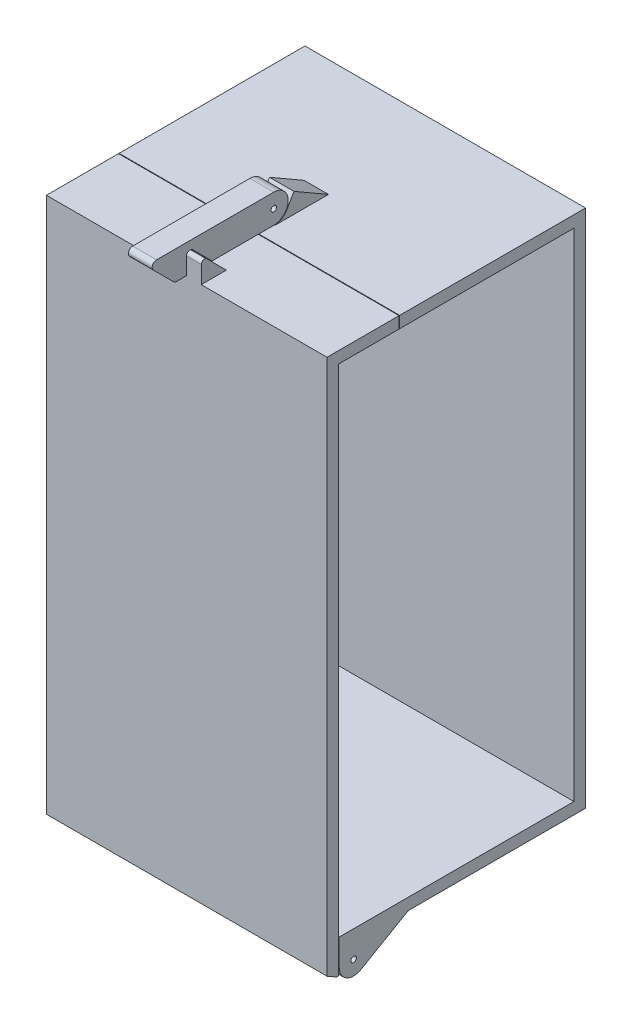
SolidWorks part; units mm, degrees
ref_plane "Front Plane" through (0, 0, 0) normal (1, 0, 0) x (0, 1, 0)
ref_plane "Top Plane" through (0, 0, 0) normal (0, 0, 1) x (0, 1, 0)
ref_plane "Right Plane" through (0, 0, 0) normal (0, 1, 0) x (-1, 0, 0)
sketch "Sketch1" plane through (0, 0, 0) normal (1, 0, 0) x (0, 1, 0)
  line L0 (5.15, 4.95) -> (5.15, -79.812)
  line L1 (5.15, -79.812) -> (184.028, -79.812)
  line L2 (184.028, -79.812) -> (184.028, -15.85)
  line L3 (184.028, -15.85) -> (180.028, -15.85)
  line L4 (180.028, -15.85) -> (180.028, -75.812)
  line L5 (180.028, -75.812) -> (9.15, -75.812)
  line L6 (9.15, -75.812) -> (9.15, 4.95)
  line L7 (9.15, 4.95) -> (5.15, 4.95)
  line L8 (9.15, -75.812) -> (5.15, -79.812) construction
  line L9 (180.028, -75.812) -> (184.028, -79.812) construction
  line L10 (0, -4.95) -> (5.15, -4.95)
  line L11 (5.15, 4.95) -> (0, 4.95)
  line L12 (180.028, -15.85) -> (9.15, -15.85) construction
  line L13 (9.15, 4.95) -> (39.15, 4.95)
  line L14 (49.2687, 3.9154) -> (139.9093, -14.8154)
  line L15 (150.028, -15.85) -> (180.028, -15.85)
  line L16 (94.589, -5.45) -> (94.589, -15.85) construction
  line L17 (-4.95, 0) -> (-4.95, 9.15)
  line L18 (-4.95, 9.15) -> (184.028, 9.15)
  line L19 (184.028, 9.15) -> (184.028, -15.65)
  line L20 (184.028, -15.65) -> (180.028, -15.65)
  line L21 (180.028, -15.65) -> (180.028, 5.15)
  line L22 (180.028, 5.15) -> (4.95, 5.15)
  line L23 (180.028, 5.15) -> (184.028, 9.15) construction
  line L24 (4.95, 5.15) -> (4.95, 0)
  line L25 (180.028, -15.65) -> (150.028, -15.65)
  line L26 (139.9498, -14.6196) -> (49.3092, 4.1113)
  line L27 (-4.2868, -2.475) -> (5.15, -18.8201)
  line L28 (-4.2868, 2.475) -> (-0.433, 9.15)
  line L29 (184.028, -15.85) -> (189.178, -15.85)
  line L30 (193.4648, -23.275) -> (184.028, -39.6201)
  line L31 (184.228, -20.8) -> (184.228, 12.6393)
  line L32 (194.128, -20.8) -> (194.128, 19.5393)
  line L33 (191.5673, 20.6) -> (184.6673, 13.7)
  line L34 (184.028, 9.15) -> (190.028, 9.15)
  line L35 (190.8058, 7.2722) -> (184.028, 0.4944)
  line L36 (184.228, 9.15) -> (190.7208, 9.15)
  line L37 (190.9472, 7.1308) -> (184.228, 0.4115)
  line L38 (184.228, -15.65) -> (189.178, -15.65)
  line L39 (191.753, -16.34) -> (194.128, -17.7112)
  line L40 (4.95, 5.15) -> (-1.8764, 5.15)
  line L41 (5.15, -5.15) -> (-1.8764, -5.15)
  line L42 (190.8898, -27.735) -> (186.603, -25.26)
  circle A0 centre (0, 0) radius 0.95
  circle A1 centre (0, 0) radius 4.95
  arc A2 (39.15, 4.95) -> (49.2687, 3.9154) centre (39.15, -45.05) cw
  arc A3 (139.9093, -14.8154) -> (150.028, -15.85) centre (150.028, 34.15) ccw
  arc A4 (150.028, -15.65) -> (139.9498, -14.6196) centre (150.028, 34.15) cw
  arc A5 (49.3092, 4.1113) -> (39.15, 5.15) centre (39.15, -45.05) ccw
  circle A6 centre (189.178, -20.8) radius 0.95
  circle A7 centre (189.178, -20.8) radius 4.95
  arc A8 (194.128, 19.5393) -> (191.5673, 20.6) centre (192.628, 19.5393) ccw
  arc A9 (184.6673, 13.7) -> (184.228, 12.6393) centre (185.728, 12.6393) ccw
  arc A10 (190.028, 9.15) -> (190.8058, 7.2722) centre (190.028, 8.05) cw
  arc A11 (190.7208, 9.15) -> (190.9472, 7.1308) centre (190.028, 8.05) cw
  arc A12 (189.178, -15.65) -> (191.753, -16.34) centre (189.178, -20.8) cw
  arc A13 (-1.8764, 5.15) -> (-2.3094, 5.9) centre (-1.8764, 5.65) cw
  arc A14 (-1.8764, -5.15) -> (-2.3094, -5.9) centre (-1.8764, -5.65) ccw
  arc A15 (186.603, -25.26) -> (184.028, -20.8) centre (189.178, -20.8) cw
  point P48 (184.228, -20.8)
  point P59 (191.128, 8.05)
  point P70 (188.1173, 17.15)
  point P84 (0, 0)
  dimension "D1" = 1.9
  dimension "D9" = 50
  dimension "D14" = 1.9
  dimension "D18" = 1.5
  dimension "D25" = 0.5
  dimension "D26" = 0.5
  dimension "D2" = 4
  dimension "D3" = 0.2
  dimension "D4" = 4
  dimension "D5" = 0.2
  dimension "D6" = 80.962
  dimension "D7" = 170.878
  dimension "D10" = 30
  dimension "D11" = 30
  dimension "D12" = 30
  dimension "D13" = 0.2
  dimension "D15" = 4
  dimension "D16" = 25
  dimension "D17" = 45
  dimension "D8" = 30
  dimension "D19" = 45
  dimension "D20" = 3
  dimension "D21" = 6
  dimension "D22" = 0.2
  dimension "D23" = 8
  dimension "D24" = 60
  dimension "D27" = 0.2
  dimension "D28" = 0.2
extrude "Boss-Extrude1" add sketch "Sketch1" against normal blind 92.551 contours L6 L7 L0 L1 L2 L3 L4 L5 | A1 L11 L24 L22 L21 L20 L19 L18 L28 | L41 A14 L27 L0 region at (0, 7.15, 2.9706) region at (0, 2.5349, -9.7206) region at (0, 100.3909, 5.8969)
extrude "Boss-Extrude2" add sketch "Sketch1<3>" against normal blind 4 from surface contours A3 L14 A2 L13 L6 L5 L4 L15 | L6 L7 L0 L1 L2 L3 L4 L5 | A1 L11 L24 L22 L21 L20 L19 L18 L28 | A5 L26 A4 L25 L21 L22 | L41 A14 L27 L0 region at (0, 7.15, 2.9706) region at (0, 89.0124, -40.1657) region at (0, 2.5349, -9.7206) region at (0, 100.3909, 5.8969) region at (0, 132.3263, -3.1974) starting at face at (-92.551, 63.5508, -30.6619)
sketch "Sketch1<3>" plane through (0, 0, 0) normal (1, 0, 0) x (0, 1, 0) same geometry as "Sketch1"
extrude "Boss-Extrude3" add sketch "Sketch1<4>" along normal blind 26.9146 from surface contours A1 A0 | L40 A13 L28 A1 L11 L24 | A1 L24 L11 region at (0, 3.8443, 3.8443) region at (0, 2.475, 5.0485) region at (0, -2.405, -4.1656) starting at face at (-96.551, 82.4064, -0.8257)
sketch "Sketch1<4>" plane through (0, 0, 0) normal (1, 0, 0) x (0, 1, 0) same geometry as "Sketch1"
ref_plane "Plane1" through (-69.4364, 0, 0) normal (1, 0, 0) x (0, 1, 0)
extrude "Boss-Extrude4" add sketch "Sketch1<6>" along normal blind 26.9146 from surface contours A1 A0 | A1 L24 L11 | A1 L10 L0 L11 L24 | A14 L41 L0 L10 A1 L27 region at (0, 4.1741, -2.7927) region at (0, 5.0496, -5.05) region at (0, 3.8443, 3.8443) region at (0, -2.405, -4.1656) starting at plane "Plane1"
sketch "Sketch1<6>" plane through (0, 0, 0) normal (1, 0, 0) x (0, 1, 0) same geometry as "Sketch1"
ref_plane "Plane2" through (-42.3219, 0, 0) normal (1, 0, 0) x (0, 1, 0)
extrude "Boss-Extrude5" add sketch "Sketch1<7>" along normal blind 26.9146 from surface contours L40 A13 L28 A1 L11 L24 | A1 A0 | A1 L24 L11 region at (0, 3.8443, 3.8443) region at (0, 2.475, 5.0485) region at (0, -2.405, -4.1656) starting at plane "Plane2"
sketch "Sketch1<7>" plane through (0, 0, 0) normal (1, 0, 0) x (0, 1, 0) same geometry as "Sketch1"
ref_plane "Plane3" through (-15.2073, 0, 0) normal (1, 0, 0) x (0, 1, 0)
extrude "Boss-Extrude6" add sketch "Sketch1<8>" along normal up to surface from surface contours A1 A0 | A1 L10 L0 L11 L24 | A1 L24 L11 | A14 L41 L0 L10 A1 L27 region at (0, 4.1741, -2.7927) region at (0, 5.0496, -5.05) region at (0, 3.8443, 3.8443) region at (0, -2.405, -4.1656) up to face at (0, 63.5508, -30.6619) starting at plane "Plane3"
sketch "Sketch1<8>" plane through (0, 0, 0) normal (1, 0, 0) x (0, 1, 0) same geometry as "Sketch1"
ref_plane "Plane4" through (-48.2755, 0, 0) normal (1, 0, 0) x (0, 1, 0)
extrude "Boss-Extrude7" add sketch "Sketch1<9>" along normal mid plane 10 from surface contours A10 L34 L31 L35 | L35 L31 L34 L19 region at (0, 184.1276, 4.872) region at (0, 186.8519, 6.2297) starting at plane "Plane4"
sketch "Sketch1<9>" plane through (0, 0, 0) normal (1, 0, 0) x (0, 1, 0) same geometry as "Sketch1"
extrude "Boss-Extrude8" add sketch "Sketch1<10>" along normal up to surface (-48.2755 mm away) and the other way blind 0.2 from surface separate body contours L38 A12 L39 L32 A8 L33 A9 L31 L34 L36 A11 L37 | A12 L38 L31 L29 A7 L32 L39 | A7 A6 | A7 L29 L31 region at (0, 184.3396, -15.75) region at (0, 185.3337, -16.9557) region at (0, 192.5792, -17.3988) region at (0, 189.729, 0.4065) up to plane "Plane4" starting at face at (-53.2755, 187.3793, 6.5816)
sketch "Sketch1<10>" plane through (0, 0, 0) normal (1, 0, 0) x (0, 1, 0) same geometry as "Sketch1"
extrude "Boss-Extrude9" add sketch "Sketch1<11>" against normal blind 3 from surface contours A7 A6 | A7 L29 L31 | A12 L38 L31 L29 A7 L32 L39 | L38 A12 L39 L32 A8 L33 A9 L31 L34 L36 A11 L37 | A10 L34 L31 L35 | A11 L36 A10 L35 L31 L37 region at (0, 184.3396, -15.75) region at (0, 185.3337, -16.9557) region at (0, 192.5792, -17.3988) region at (0, 189.729, 0.4065) region at (0, 186.8519, 6.2297) region at (0, 184.3406, 0.5529) starting at face at (-53.4755, 189.178, -21.75)
sketch "Sketch1<11>" plane through (0, 0, 0) normal (1, 0, 0) x (0, 1, 0) same geometry as "Sketch1"
extrude "Boss-Extrude10" add sketch "Sketch1<14>" along normal up to surface (-48.2755 mm away) and the other way blind 0.2 from surface contours L42 A15 L2 L30 region at (0, 186.2706, -30.1995) up to plane "Plane4" starting at face at (-56.4755, 189.178, -21.75)
sketch "Sketch1<14>" plane through (0, 0, 0) normal (1, 0, 0) x (0, 1, 0) same geometry as "Sketch1"
equation "\"L\"= 7.13in"
equation "\"W\" = 3.03in"
equation "\"H\"= 6.57in"
equation "\"gap\"= 2"
equation "\"tol\"= 0.2"
equation "\"wall\"= 4"
equation "\"D2@Sketch1\"=\"wall\""
equation "\"D3@Sketch1\"=\"tol\""
equation "\"D4@Sketch1\"=\"wall\""
equation "\"D5@Sketch1\"=\"tol\""
equation "\"D6@Sketch1\"=\"W\"+\"gap\"*2"
equation "\"D7@Sketch1\"=\"H\"+\"gap\"*2"
equation "\"D13@Sketch1\"=\"tol\""
equation "\"D14@Sketch1\"=\"D1@Sketch1\""
equation "\"D15@Sketch1\"=\"wall\""
equation "\"D20@Sketch1\"=\"wall\"*3/4"
equation "\"D21@Sketch1\"=\"wall\"*3/2"
equation "\"D22@Sketch1\"=\"tol\""
equation "\"D23@Sketch1\"=\"wall\"*2"
equation "\"D1@Boss-Extrude1\"=\"L\"/2+\"gap\""
equation "\"D1@Boss-Extrude2\"=\"wall\""
equation "\"D25@Sketch1\"=\"wall\"/8"
equation "\"D26@Sketch1\"=\"D25@Sketch1\""
equation "\"D27@Sketch1\"=\"tol\""
equation "\"D1@Boss-Extrude3\"=(\"L\"+\"gap\"*2+\"wall\")/7-\"tol\"/2"
equation "\"D1@Boss-Extrude4\"=(\"L\"+\"gap\"*2+\"wall\")/7-\"tol\"/2"
equation "\"D1@Boss-Extrude5\"=(\"L\"+\"gap\"*2+\"wall\")/7-\"tol\"/2"
equation "\"so\"= 10"
equation "\"D1@Boss-Extrude7\"=\"so\""
equation "\"D2@Boss-Extrude8\"=\"tol\""
equation "\"D1@Boss-Extrude9\"=\"wall\"*3/4"
equation "\"D28@Sketch1\"=\"tol\""
equation "\"D2@Boss-Extrude10\"=\"tol\""
